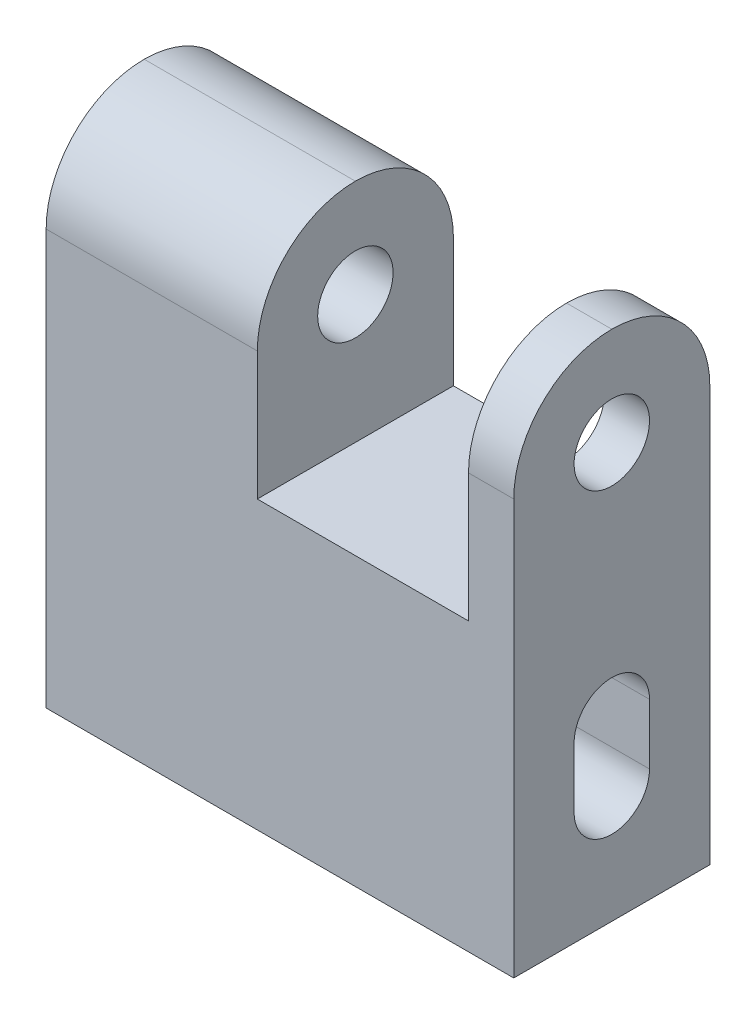
SolidWorks part; units mm, degrees
ref_plane "Ön Düzlem" through (0, 0, 0) normal (0, 0, 1) x (1, 0, 0)
ref_plane "Üst Düzlem" through (0, 0, 0) normal (0, 1, 0) x (1, 0, 0)
ref_plane "Sağ Düzlem" through (0, 0, 0) normal (1, 0, 0) x (0, 0, -1)
sketch "Sketch2" plane through (0, 0, 0) normal (0, 0, 1) x (1, 0, 0)
  line L0 (0, 0) -> (0, -34)
  line L1 (0, -34) -> (31, -34)
  line L2 (31, -34) -> (31, 0)
  line L3 (31, 0) -> (28, 0)
  line L4 (28, 0) -> (28, -15)
  line L5 (28, -15) -> (14, -15)
  line L6 (14, -15) -> (14, 0)
  line L7 (14, 0) -> (0, 0)
  line L8 (15.5, -34) -> (15.5, -21.5) construction
  dimension "D1" = 14
  dimension "D2" = 3
  dimension "D3" = 14
  dimension "D4" = 15
  dimension "D5" = 34
extrude "Boss-Extrude1" add sketch "Sketch2" along normal blind 13
sketch "Sketch4" plane through (0, 0, 0) normal (-1, 0, 0) x (0, 0, 1)
  line L0 (13, -34) -> (0, -34) construction
  line L1 (0, 0) -> (0, -34) construction
  line L2 (6.5, -24.5) -> (0, -24.5) construction
  line L3 (6.5, -26.5) -> (6.5, -22.5) construction
  line L4 (4, -26.5) -> (4, -22.5)
  line L5 (9, -26.5) -> (9, -22.5)
  arc A0 (4, -26.5) -> (9, -26.5) centre (6.5, -26.5) ccw
  arc A1 (9, -22.5) -> (4, -22.5) centre (6.5, -22.5) ccw
  point P8 (6.5, -24.5)
  point P20 (0, 0)
  dimension "D2" = 2
  dimension "D4" = 2.5
  dimension "D1" = 9.5
  dimension "D3" = 6.5
extrude "Cut-Extrude1" cut sketch "Sketch4" against normal through all contours L5 A1 L4 A0
sketch "Sketch5" plane through (31, 0, 0) normal (1, 0, 0) x (0, 0, -1)
  line L3 (0, -34) -> (0, 0) construction
  line L4 (-13, 0) -> (0, 0) construction
  circle A0 centre (-6.5, -6.5) radius 2.5
  dimension "D2" = 5
  dimension "D1" = 6.5
  dimension "D4" = 6.5
extrude "Cut-Extrude2" cut sketch "Sketch5" against normal through all and the other way through all
fillet "Fillet1" radius 6.5 4 edges at (29.5, 0, 13) (7, 0, 13) (7, 0, 0) (29.5, 0, 0)
sketch "Sketch6" plane through (0, -34, 0) normal (0, -1, 0) x (1, 0, 0)
  line L0 (0, 6.5) -> (31, 6.5) construction
  line L1 (0, 13) -> (0, 0) construction
  line L2 (31, 13) -> (31, 0) construction
  circle A0 centre (15.5, 6.5) radius 2
  dimension "D1" = 4
extrude "Cut-Extrude3" cut sketch "Sketch6" against normal blind 8
